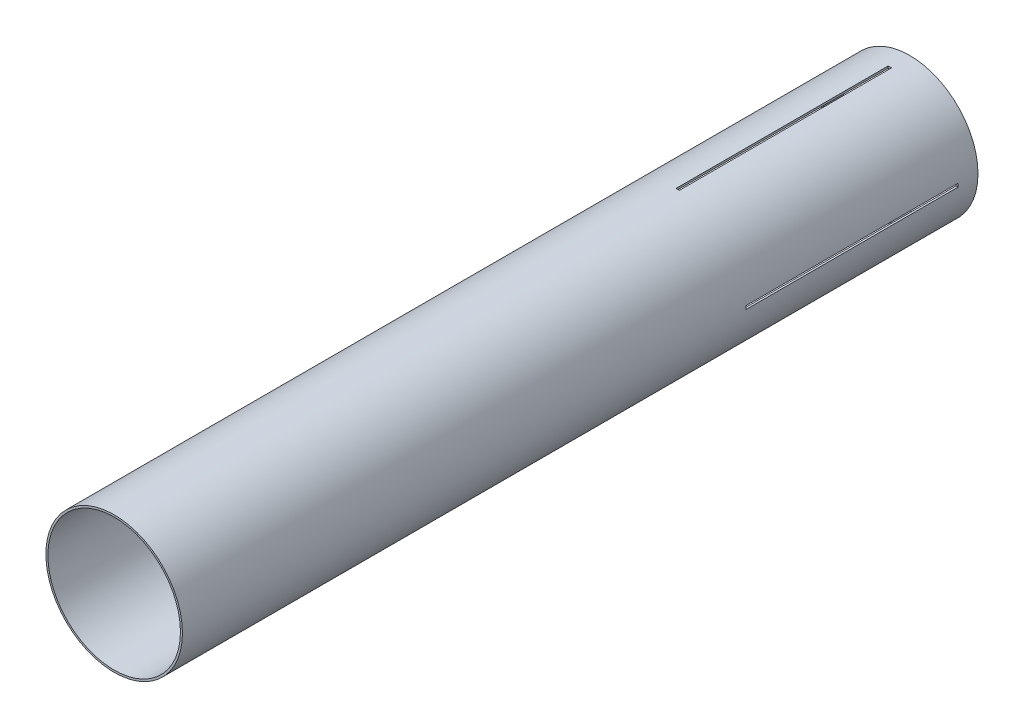
SolidWorks part; units mm, degrees
ref_plane "Front Plane" through (0, 0, 0) normal (0, 0, 1) x (1, 0, 0)
ref_plane "Top Plane" through (0, 0, 0) normal (0, 1, 0) x (1, 0, 0)
ref_plane "Right Plane" through (0, 0, 0) normal (1, 0, 0) x (0, 0, -1)
sketch "Sketch1" plane through (0, 0, 0) normal (0, 0, 1) x (1, 0, 0)
  circle A0 centre (0, 0) radius 65.405
  circle A1 centre (0, 0) radius 63.5
  dimension "D1" = 127
  dimension "D2" = 130.81
extrude "Boss-Extrude1" add sketch "Sketch1" along normal mid plane 762
sketch "Sketch3" plane through (0, 0, 0) normal (0, 1, 0) x (1, 0, 0)
  line L0 (65.405, 381) -> (-65.405, 381) construction
  line L1 (1.5875, 158.75) -> (-1.5875, 158.75)
  line L2 (1.5875, 158.75) -> (1.5875, 361.95)
  line L3 (1.5875, 361.95) -> (-1.5875, 361.95)
  line L4 (-1.5875, 158.75) -> (-1.5875, 361.95)
  line L5 (1.5875, 158.75) -> (-1.5875, 361.95) construction
  line L6 (1.5875, 361.95) -> (-1.5875, 158.75) construction
  line L7 (65.405, 381) -> (-65.405, 381) construction
  point P0 (0, 260.35)
  dimension "D2" = 203.2
  dimension "D3" = 19.05
extrude "Cut-Extrude1" cut sketch "Sketch3" along normal through all
pattern_circular "CirPattern1" count 4 over 360 about axis through (0, 0, 381) along (0, 0, -1) of "Cut-Extrude1" reverse direction yes
equation "\"AIRFRAME_OD\"= 5.15in"
equation "\"AIRFRAME_ID\"= 5.00in"
equation "\"FLAT_T\"= 0.125in"
equation "\"NOSE_EXP_L\"= 27in"
equation "\"NOSE_SHOULDER_L\"= 5in"
equation "\"MAIN_L\"= 30in"
equation "\"RECO_COUP_L\"= 10in"
equation "\"RECO_SWITCH_L\"= 2in"
equation "\"DROGUE_L\"= 20in"
equation "\"ATS_FORE_COUP_L\"= 5.5in"
equation "\"ATS_AFT_COUP_L\"= 4.5in"
equation "\"LOWER_L\"= 30in"
equation "\"FIN_N\"= 4"
equation "\"CR_AFT_X\"= 0.5in"
equation "\"CR_FORE_X\"= 9.25in"
equation "\"D1@Sketch1\"=\"AIRFRAME_ID\""
equation "\"D2@Sketch1\"=\"AIRFRAME_OD\""
equation "\"D1@Boss-Extrude1\"=\"LOWER_L\""
equation "\"FIN_ROOT\"= 8in"
equation "\"FIN_X\"= 0.75in"
equation "\"MOTOR_OD\"= 3.091in"
equation "\"MOTOR_ID\"= 3.00in"
equation "\"D1@Sketch3\"=\"FLAT_T\""
equation "\"D2@Sketch3\"=\"FIN_ROOT\""
equation "\"D3@Sketch3\"=\"FIN_X\""
equation "\"D1@CirPattern1\"=\"FIN_N\""
equation "\"COUPLER_OD\"= 4.998in"
equation "\"COUPLER_ID\"= 4.88in"
equation "\"RECO_ROD_X\"= 3.5in"
equation "\"ATS_ROD_X\"= 3.75in"
equation "\"MOTOR_L\"= 14in"
equation "\"MOTOR_LOWER_X\"= 2in"
